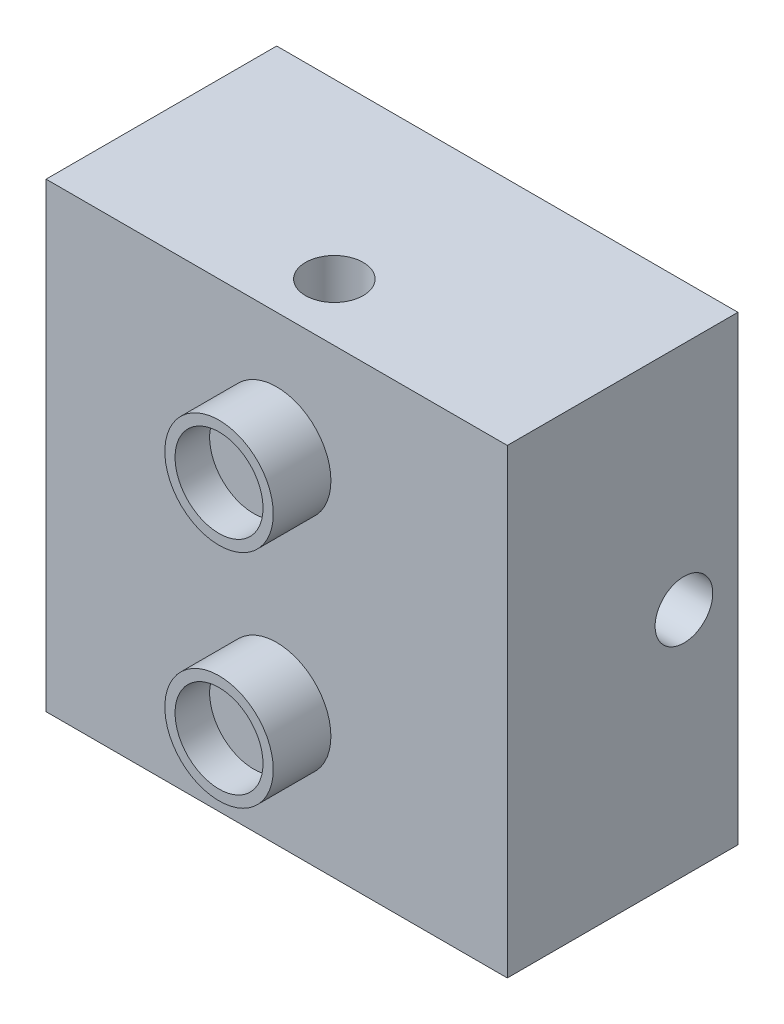
SolidWorks part; units mm, degrees
ref_plane "Front Plane" through (0, 0, 0) normal (0, 0, 1) x (1, 0, 0)
ref_plane "Top Plane" through (0, 0, 0) normal (0, 1, 0) x (1, 0, 0)
ref_plane "Right Plane" through (0, 0, 0) normal (1, 0, 0) x (0, 0, -1)
sketch "Sketch1" plane through (0, 0, 0) normal (0, 0, 1) x (1, 0, 0)
  line L1 (-50.8, 50.8) -> (50.8, 50.8)
  line L2 (-50.8, 50.8) -> (-50.8, -50.8)
  line L3 (-50.8, -50.8) -> (50.8, -50.8)
  line L4 (50.8, 50.8) -> (50.8, -50.8)
  line L5 (-50.8, 50.8) -> (50.8, -50.8) construction
  line L6 (-50.8, -50.8) -> (50.8, 50.8) construction
  point P0 (0, 0)
  dimension "D1" = 101.6
  dimension "D2" = 101.6
extrude "Boss-Extrude1" add sketch "Sketch1" along normal blind 50.8
sketch "Sketch2" plane through (0, 50.8, 0) normal (0, 1, 0) x (1, 0, 0)
  line L0 (50.8, -50.8) -> (-50.8, -50.8) construction
  circle A0 centre (0, -38.1) radius 6.35
  dimension "D1" = 12.7
  dimension "D2" = 12.7
extrude "Cut-Extrude1" cut sketch "Sketch2" against normal blind 254
sketch "Sketch3" plane through (50.8, 0, 0) normal (1, 0, 0) x (0, 0, -1)
  circle A0 centre (-11.8913, 0) radius 6.35
  dimension "D1" = 12.7
extrude "Cut-Extrude2" cut sketch "Sketch3" against normal blind 254
sketch "Sketch4" plane through (0, 0, 50.8) normal (0, 0, 1) x (1, 0, 0)
  circle A0 centre (0, 24.639) radius 11.9414
  circle A1 centre (0, -24.1238) radius 11.9414
extrude "Boss-Extrude2" add sketch "Sketch4" along normal blind 12.7
sketch "Sketch5" plane through (0, 0, 63.5) normal (0, 0, 1) x (1, 0, 0)
  circle A0 centre (0, 24.639) radius 9.6887
  circle A1 centre (0, -24.1238) radius 9.6887
extrude "Cut-Extrude3" cut sketch "Sketch5" against normal blind 7.62
